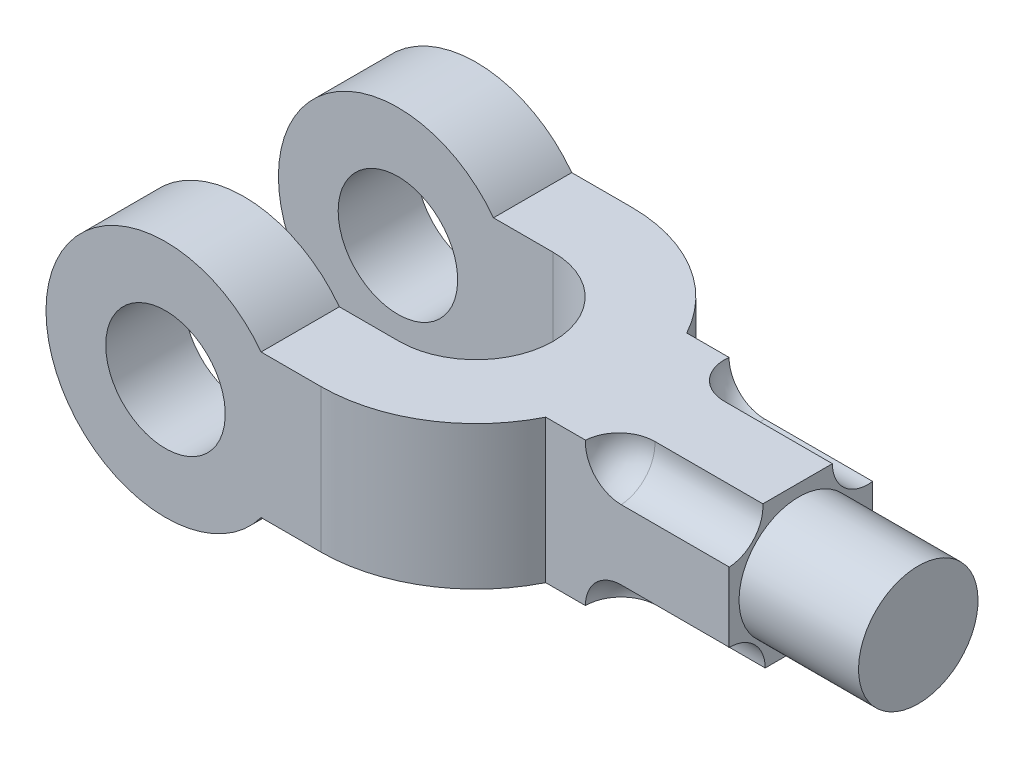
SolidWorks part; units mm, degrees
ref_plane "Front Plane" through (0, 0, 0) normal (0, 0, 1) x (1, 0, 0)
ref_plane "Top Plane" through (0, 0, 0) normal (0, 1, 0) x (1, 0, 0)
ref_plane "Right Plane" through (0, 0, 0) normal (1, 0, 0) x (0, 0, -1)
sketch "Sketch1" plane through (0, 0, 0) normal (0, 0, 1) x (1, 0, 0)
  line L1 (16, 12) -> (80, 12)
  line L2 (16, -12) -> (80, -12)
  line L3 (80, 12) -> (80, -12)
  line L4 (80, 0) -> (100, 0)
  line L5 (80, 10) -> (100, 10)
  line L8 (100, 10) -> (100, 0)
  line L9 (80, -10) -> (80, 10) construction
  line L10 (80, 0) -> (100, 0) construction
  line L11 (52, 12) -> (52, -12)
  circle A2 centre (0, 0) radius 10
  arc A3 (16, 12) -> (16, -12) centre (0, 0) ccw
  point P3 (80, 0)
  dimension "D1" = 28
  dimension "D2" = 40
  dimension "D3" = 64
  dimension "D4" = 20
  dimension "D5" = 24
revolve "Revolve1" add sketch "Sketch1" angle 360 about L4 region at (90, 5, 0)
extrude "Boss-Extrude4" add sketch "Sketch1<8>" along normal mid plane 52 contours L1 A3 L2 L11 A2 | L1 L11 L2 L3 region at (16.2107, 0, 0) region at (66, 0, 0)
sketch "Sketch1<8>" plane through (0, 0, 0) normal (0, 0, 1) x (1, 0, 0) same geometry as "Sketch1"
sketch "Sketch4" plane through (0, 0, 0) normal (0, 1, 0) x (1, 0, 0)
  line L1 (-20, 26) -> (-20, -26) construction
  line L2 (80, 12.378) -> (48.8645, 12.378)
  line L3 (26, 26) -> (26, -26)
  line L4 (26, 12.9013) -> (-20, 12.9013)
  line L5 (26, -12.9013) -> (-20, -12.9013)
  line L6 (-20, -12.9013) -> (-20, 12.9013)
  line L7 (79.9067, -11.622) -> (49.2579, -11.622)
  line L8 (26, -26) -> (80, -26)
  line L9 (80, -26) -> (79.9067, -11.622)
  line L10 (26, 26) -> (80, 26)
  line L11 (80, 26) -> (80, -26)
  arc A0 (26, -12.9013) -> (26, 12.9013) centre (26, 0) ccw
  arc A1 (26, -26) -> (26, 26) centre (26, 0) ccw
  point P5 (66.3418, 0.378)
extrude "Cut-Extrude2" cut sketch "Sketch4" against normal mid plane 52 contours L6 L5 L3 L4 | L3 A0 | A1 L2 L11 L10 | A1 L8 L9 L7 region at (60.7745, 0, -19.7144) region at (60.9143, 0, 19.3823) region at (31.4755, 0, 0) region at (3, 0, 0)
sketch "Sketch5" plane through (80, 0, 0) normal (1, 0, 0) x (0, 0, -1)
  line L0 (-26, 0) -> (-11.6673, 0)
  line L1 (-26, 12) -> (-26, -12) construction
  line L3 (-11.6673, 12) -> (-26, 12)
  line L4 (-11.6673, 12) -> (-11.6673, -12)
  line L5 (-11.6673, -12) -> (-26, -12)
  line L6 (-26, 12) -> (-26, -12)
  line L7 (-18.8336, -12) -> (-18.8336, 12) construction
  line L8 (-11.6673, 0) -> (-26, 0) construction
  point P5 (-18.8336, 0)
  line M2 (-26, -12) -> (12.378, -12)
  line M4 (12.378, 12) -> (-26, 12)
  line M5 (-26, 12) -> (-26, -12)
extrude "Cut-Extrude3" cut sketch "Sketch5" against normal blind 10 contours L4 L0 M4 M5 | L4 L0 M5 M2 region at (80, 6, 18.8336) region at (80, -6, 18.8336)
sketch "Sketch6" plane through (0, 0, 11.622) normal (0, 0, 1) x (1, 0, 0)
  line L0 (81.079, -12) -> (61.9067, -12)
  line L1 (79.9067, -12) -> (49.2579, -12) construction
  line L2 (61.9067, -12) -> (55.9067, -12)
  line L3 (61.9067, -12) -> (61.9067, -6)
  line L4 (61.9067, -6) -> (80.4408, -6)
  line L5 (80.4408, -6) -> (81.079, -12)
  arc A0 (61.9067, -6) -> (55.9067, -12) centre (61.9067, -12) ccw
  dimension "D2" = 12
revolve "Cut-Revolve3" cut sketch "Sketch6" angle 360 about L0 region at (70.9067, -9, 11.622) region at (59.3602, -9.4535, 11.622)
sketch "Sketch7" plane through (79.9067, 0, 0) normal (-1, 0, 0) x (0, 0, 1)
  circle A0 centre (11.622, -12) radius 6
extrude "Cut-Extrude4" cut sketch "Sketch7" against normal blind 10
pattern_circular "CirPattern2" count 4 over 360 about axis through (81.079, -12, 11.622) along (1, 0, 0) of "Cut-Revolve3" reverse direction yes
pattern_circular "CirPattern3" count 4 over 360 about axis through (100, 0, 0) along (-1, 0, 0) of "Cut-Extrude4", "Cut-Revolve3"
